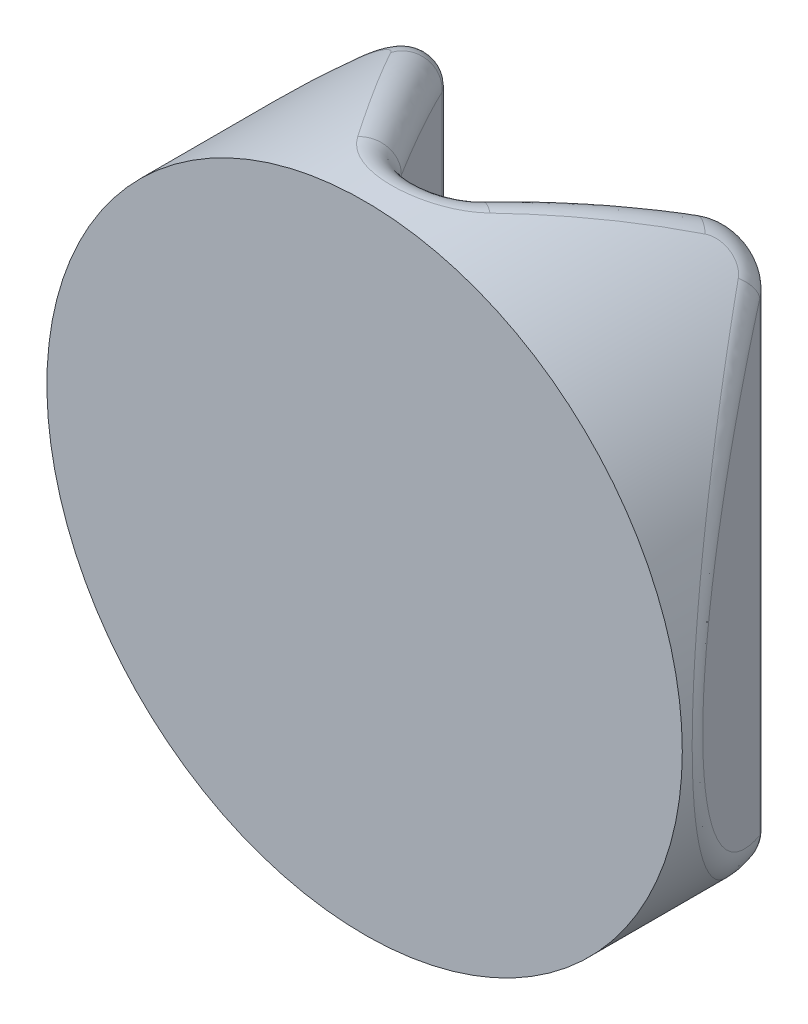
SolidWorks part; units mm, degrees
ref_plane "Plan de face" through (0, 0, 0) normal (0, 0, 1) x (1, 0, 0)
ref_plane "Plan de dessus" through (0, 0, 0) normal (0, 1, 0) x (1, 0, 0)
ref_plane "Plan de droite" through (0, 0, 0) normal (1, 0, 0) x (0, 0, -1)
sketch "Esquisse1" plane through (0, 0, 0) normal (0, 0, 1) x (1, 0, 0)
  circle A0 centre (0, 0) radius 34.9
  dimension "D1" = 69.8
extrude "Boss.-Extru.1" add sketch "Esquisse1" along normal blind 28
sketch "Esquisse2" plane through (0, 0, 0) normal (0, 1, 0) x (1, 0, 0)
  line L0 (0, 0) -> (0, -50000) construction
  line L1 (-34.9, -28) -> (34.9, -28) construction
  line L2 (-17.45, 0) -> (0, -26)
  line L3 (34.9, 0) -> (-34.9, 0) construction
  line L4 (-34.9, -26) -> (-17.45, 0)
  line L5 (-34.9, -1026) -> (-34.9, 48974) construction
  line L6 (-34.9, 0) -> (-34.9, -28) construction
  line L7 (17.45, 0) -> (0, -26)
  line L8 (34.9, -26) -> (17.45, 0)
  line L9 (-34.9, -26) -> (-34.9, 0)
  line L10 (-34.9, 0) -> (34.9, 0)
  line L11 (34.9, 0) -> (34.9, -26)
  point P5 (0, -28)
  point P7 (0, -26)
  point P10 (-17.45, 0)
  point P11 (-34.9, -26)
  point P19 (0, 0)
  dimension "D1" = 2
  dimension "D2" = 2
  dimension "D3" = 17.45
extrude "Enlèv. mat.-Extru.1" cut sketch "Esquisse2" against normal through all both and the other way through all contours L10 L9 L4 | L10 L2 L7 | L11 L10 L8 region at (0, 0, 8.6667) region at (-29.0833, 0, 8.6667) region at (29.0833, 0, 8.6667)
fillet "Congé1" radius 5 2 edges at (17.45, 0, 0) (-17.45, 0, 0)
fillet "Congé2" radius 5 1 edges at (0, 0, 26)
fillet "Congé3" radius 3 12 edges at (16.7896, 30.5961, 4.016) (8.8061, 33.7707, 12.8791) (-17.4943, 30.1987, 3.9724) (-0.1684, 34.8996, 22.025) (-8.8061, 33.7707, 12.8791) (17.4943, -30.1987, 3.9724) (0.1684, -34.8996, 22.025) (-16.7896, -30.5961, 4.016) (-8.8061, -33.7707, 12.8791) (8.8061, -33.7707, 12.8791) (34.9, 0, 26) (-34.9, 0, 26)
